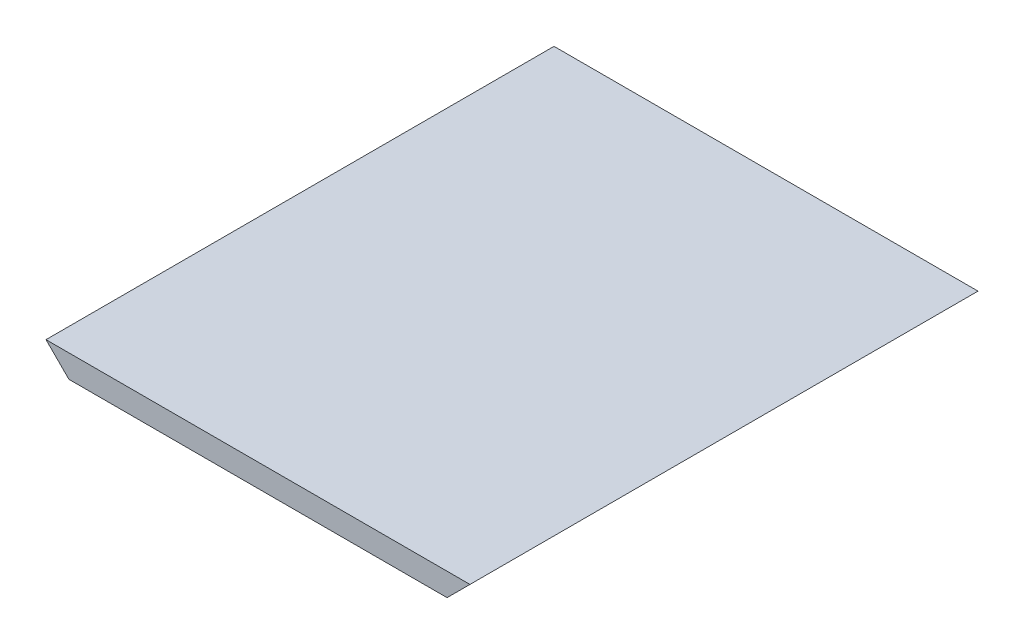
SolidWorks part; units mm, degrees
ref_plane "Front Plane" through (0, 0, 0) normal (0, 0, 1) x (1, 0, 0)
ref_plane "Top Plane" through (0, 0, 0) normal (0, 1, 0) x (1, 0, 0)
ref_plane "Right Plane" through (0, 0, 0) normal (1, 0, 0) x (0, 0, -1)
sketch "Sketch1" plane through (0, 0, 0) normal (0, 1, 0) x (1, 0, 0)
  line L0 (0, 118.0464) -> (0, -120.8757) construction
  line L1 (-169.7605, 0) -> (206.2275, 0) construction
  line L2 (-55.5, -66.5) -> (-55.5, 66.5)
  line L3 (-55.5, 66.5) -> (55.5, 66.5)
  line L4 (55.5, -66.5) -> (55.5, 66.5)
  line L5 (-55.5, -66.5) -> (55.5, -66.5)
  point P5 (0, -66.5)
  point P9 (0, 66.5)
  point P11 (55.5, 0)
  point P12 (-55.5, 0)
  dimension "D1" = 111
  dimension "D2" = 133
extrude "Boss-Extrude1" add sketch "Sketch1" along normal blind 6 contours L2 L3 L4 L5
chamfer "Chamfer1" distance 6 angle 45 2 edges at (55.5, 0, 0) (-55.5, 0, 0)
